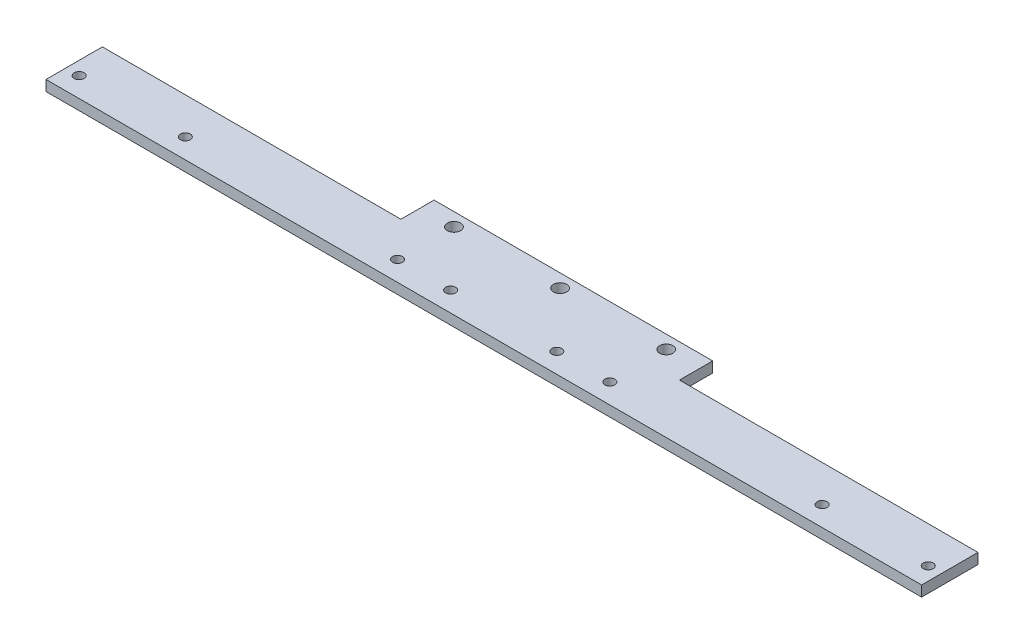
SolidWorks part; units mm, degrees
ref_plane "Front" through (0, 0, 0) normal (0, 0, 1) x (1, 0, 0)
ref_plane "Top" through (0, 0, 0) normal (0, 1, 0) x (1, 0, 0)
ref_plane "Right" through (0, 0, 0) normal (1, 0, 0) x (0, 0, -1)
sketch "Sketch1" plane through (0, 0, 0) normal (0, 1, 0) x (1, 0, 0)
  line L0 (0, 25.5356) -> (0, -1.4644)
  line L3 (0, 25.5356) -> (264, 25.5356)
  line L7 (0, -1.4644) -> (264, -1.4644)
  line L8 (264, -1.4644) -> (264, 25.5356)
  line L9 (264, -1.4644) -> (264, 10.5356)
  line L10 (264, 21.5356) -> (260, 21.5356)
  line L11 (0, 21.5356) -> (4, 21.5356)
  line L12 (4, 21.5356) -> (260, 21.5356)
  line L13 (4, 21.5356) -> (132, 21.5356)
  line L14 (132, 21.5356) -> (260, 21.5356)
  line L15 (264, 10.5356) -> (264, -1.4644)
  line L16 (264, 4.5356) -> (260, 4.5356)
  line L17 (132, 25.5356) -> (132, 23.5356)
  line L18 (4, 21.5356) -> (68, 21.5356)
  line L19 (68, 21.5356) -> (36, 21.5356)
  line L20 (36, 21.5356) -> (36, 4.5356)
  line L21 (196, 21.5356) -> (260, 21.5356)
  line L22 (228, 21.5356) -> (228, 4.5356)
  line L23 (132, 21.5356) -> (132, 4.5356)
  line L24 (132, 21.5356) -> (164, 21.5356)
  circle A0 centre (4, 21.5356) radius 2
  circle A1 centre (260, 21.5356) radius 2
  circle A2 centre (132, 21.5356) radius 2
  circle A3 centre (68, 21.5356) radius 2
  circle A4 centre (196, 21.5356) radius 2
  circle A5 centre (260, 4.5356) radius 1.5
  circle A6 centre (4, 4.5356) radius 1.5
  circle A7 centre (36, 4.5356) radius 1.5
  circle A8 centre (228, 4.5356) radius 1.5
  circle A9 centre (132, 4.5356) radius 1.5
  circle A10 centre (164, 21.5356) radius 2
  circle A11 centre (100, 21.5356) radius 2
  dimension "D5" = 23
  dimension "D6" = 128
  dimension "D9" = 4
  dimension "D10" = 32
  dimension "D1" = 4
  dimension "D2" = 264
  dimension "D3" = 4
  dimension "D4" = 4
  dimension "D7" = 128
  dimension "D8" = 12
extrude "Boss-Extrude1" add sketch "Sketch1" along normal blind 3.175 contours A1 L10 L3 A0 | A1 A0 L10 | A3 L13 A2 L17 L3 L0 L11 A0 | A9 | A0 | A1 region at (65.9183, 0, -23.5857) region at (1, 0, -18.8856) region at (198.0817, 0, -23.5857)
sketch "Sketch2" plane through (0, 3.175, 0) normal (0, 1, 0) x (1, 0, 0)
  line L0 (37.5, 4.5356) -> (228, 4.5356)
  line L1 (132, 21.5356) -> (132, 4.5356)
  line L2 (132, 4.5356) -> (148, 4.5356)
  line L3 (148, 4.5356) -> (116, 4.5356)
  line L4 (116, 4.5356) -> (100, 4.5356)
  line L5 (148, 4.5356) -> (164, 4.5356)
  circle A0 centre (36, 4.5356) radius 1.5 construction
  circle A1 centre (116, 4.5356) radius 1.5
  circle A2 centre (148, 4.5356) radius 1.5
  circle A3 centre (100, 4.5356) radius 1.5
  circle A4 centre (164, 4.5356) radius 1.5
  dimension "D3" = 16
  dimension "D1" = 16
  dimension "D2" = 16
  dimension "D4" = 16
extrude "Cut-Extrude1" cut sketch "Sketch2" against normal blind 10 contours A3 | A1 | A2 | A4
sketch "Sketch3" plane through (0, 3.175, 0) normal (0, 1, 0) x (1, 0, 0)
  line L0 (0, 25.5356) -> (0, 15.5356)
  line L1 (0, 25.5356) -> (90, 25.5356)
  line L2 (0, 15.5356) -> (90, 15.5356)
  line L3 (90, 25.5356) -> (90, 15.5356)
  line L4 (0, 25.5356) -> (0, -1.4644) construction
  line L5 (264, 25.5356) -> (264, 15.5356)
  line L6 (264, 25.5356) -> (174, 25.5356)
  line L7 (264, 15.5356) -> (174, 15.5356)
  line L8 (174, 25.5356) -> (174, 15.5356)
  line L9 (264, -1.4644) -> (264, 25.5356) construction
  line M15 (264, -1.4644) -> (264, 25.5356)
  line M16 (264, 25.5356) -> (0, 25.5356)
  line M17 (0, 25.5356) -> (0, -1.4644)
  dimension "D1" = 90
  dimension "D2" = 90
  dimension "D3" = 10
  dimension "D4" = 10
extrude "Cut-Extrude2" cut sketch "Sketch3" against normal blind 10 contours L3 L2 M16 M17 | L8 L7 M16 M15 region at (45, 3.175, -20.5356) region at (219, 3.175, -20.5356)
